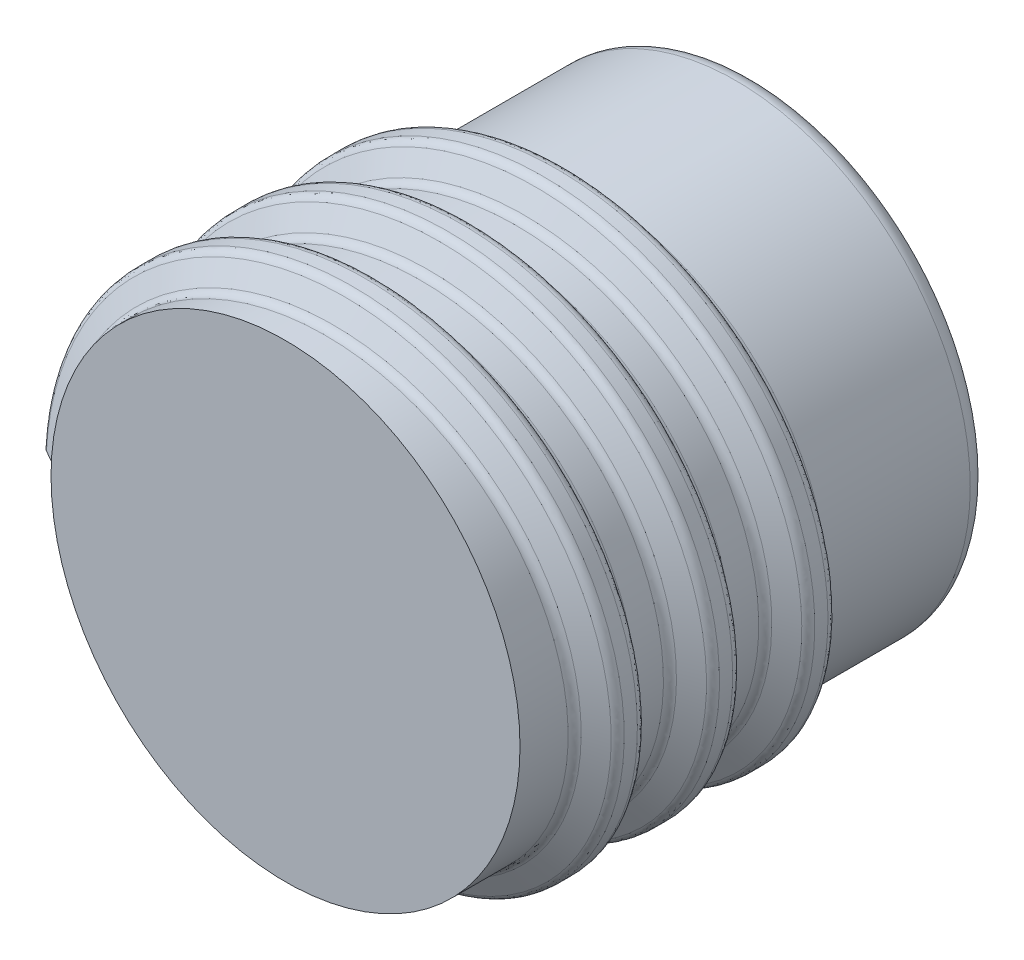
SolidWorks part; units mm, degrees
ref_plane "Ebene vorne" through (0, 0, 0) normal (0, 0, 1) x (1, 0, 0)
ref_plane "Ebene oben" through (0, 0, 0) normal (0, 1, 0) x (1, 0, 0)
ref_plane "Ebene rechts" through (0, 0, 0) normal (1, 0, 0) x (0, 0, -1)
sketch "Skizze1" plane through (0, 0, 0) normal (0, 0, 1) x (1, 0, 0)
  circle A0 centre (0, 0) radius 12.5
extrude "Aufsatz-Linear austragen1" add sketch "Skizze1" along normal blind 25
thread "Gewinde2" pitch 5.08 method extrude profile "Gewindeprofil2" start angle 0, offset 0, length 15, pitch 5.08, diameter 25
ref_plane "Ebene2" through (-12.5, 0, 25) normal (0, -1, 0) x (-1, 0, 0)
sketch "Gewindeprofil2" plane through (-12.5, 0, 25) normal (0, -1, 0) x (-1, 0, 0)
  line L0 (0, 0) -> (0, 5.08) construction
  line L1 (0, 0) -> (0, 3.6346)
  line L2 (0.508, 3.6346) -> (1.524, 3.6346) construction
  line L3 (1.524, 2.1681) -> (1.524, 1.4665)
  line L4 (1.27, 2.6081) -> (0.254, 3.1946)
  line L5 (1.27, 1.0265) -> (0.254, 0.4399)
  line L6 (0.508, 0) -> (1.524, 0) construction
  arc A0 (0.254, 3.1946) -> (0, 3.6346) centre (0.508, 3.6346) cw
  arc A1 (0.254, 0.4399) -> (0, 0) centre (0.508, 0) ccw
  arc A2 (1.524, 1.4665) -> (1.27, 1.0265) centre (1.016, 1.4665) cw
  arc A3 (1.524, 2.1681) -> (1.27, 2.6081) centre (1.016, 2.1681) ccw
  point P10 (1.524, 2.4614)
  point P17 (1.524, 1.1732)
  point P18 (0, 3.3413)
  point P19 (0, 0.2933)
  point P20 (0, 0)
  dimension "RootFillet1" = 0.508
  dimension "RootFillet2" = 0.508
  dimension "CrestFillet2" = 0.508
  dimension "CrestFillet1" = 0.508
  dimension "Pitch" = 5.08
  dimension "Angle1" = 30
  dimension "Angle2" = 30
  dimension "a" = 3.048
  dimension "b" = 1.524
  dimension "c" = 1.2882
fillet "Verrundung1" radius 1 1 edges at (12.5, 0, 0)
